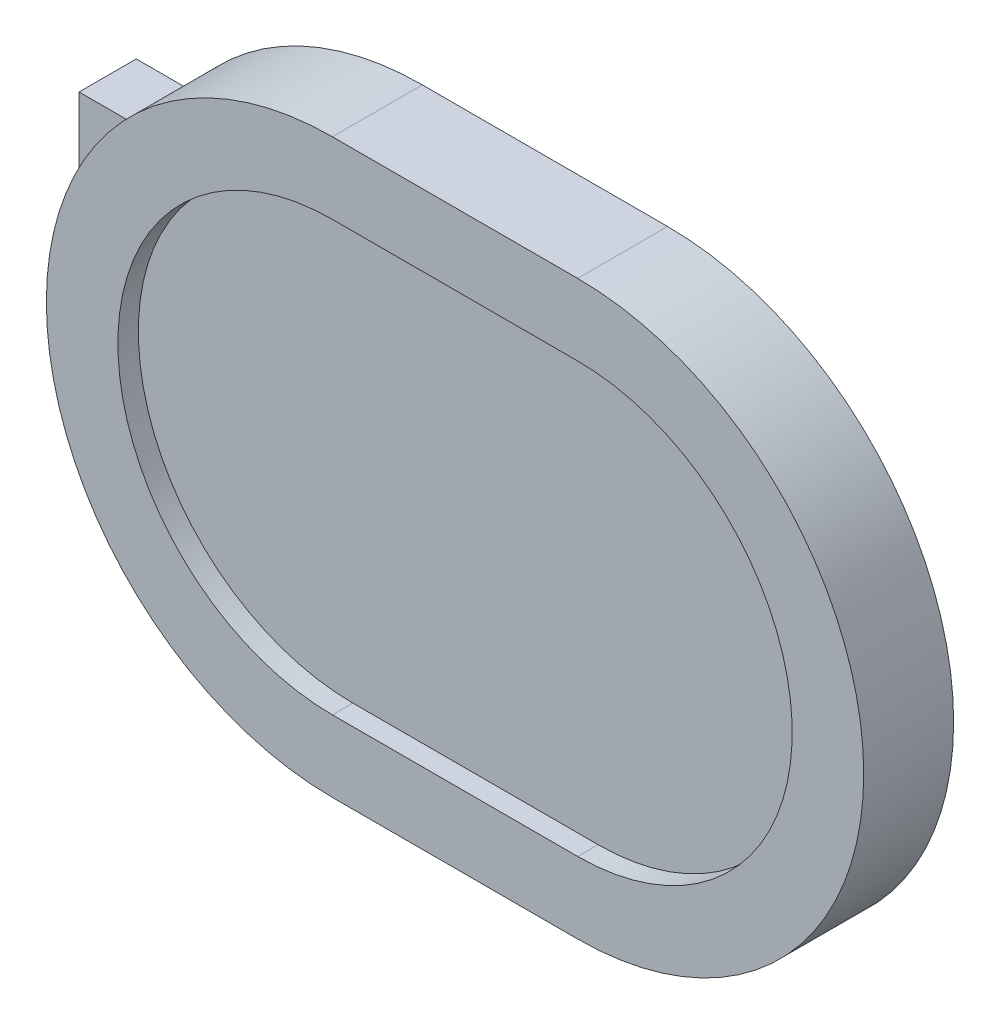
SolidWorks part; units mm, degrees
material "ABS"
ref_plane "Спереди" through (0, 0, 0) normal (0, 0, 1) x (1, 0, 0)
ref_plane "Сверху" through (0, 0, 0) normal (0, 1, 0) x (1, 0, 0)
ref_plane "Справа" through (0, 0, 0) normal (1, 0, 0) x (0, 0, -1)
ref_axis "Ось1" through (0, 0, 50) along (0, 0, -1)
sketch "Эскиз1" plane through (0, 0, 0) normal (0, 0, 1) x (1, 0, 0)
  circle A0 centre (0, 0) radius 5.3
  dimension "D1" = 10.6
extrude "Бобышка-Вытянуть1" add sketch "Эскиз1" along normal blind 0.8
sketch "Эскиз2" plane through (0, 0, 0.8) normal (0, 0, 1) x (1, 0, 0)
  line L0 (3, 0) -> (-3, 0) construction
  line L1 (3, -7) -> (-3, -7)
  line L2 (3, 7) -> (-3, 7)
  arc A0 (3, -7) -> (3, 7) centre (3, 0) ccw
  arc A1 (-3, 7) -> (-3, -7) centre (-3, 0) ccw
  point P2 (0, 0)
  point P7 (-10, 0)
  point P8 (10, 0)
  dimension "D1" = 14
  dimension "D2" = 20
extrude "Бобышка-Вытянуть2" add sketch "Эскиз2" along normal offset from surface (2.2 mm away) 3 up to face at (5.3, 0, 0)
sketch "Эскиз3" plane through (0, 0, 3) normal (0, 0, 1) x (1, 0, 0)
  line L0 (-3, 0) -> (3, 0) construction
  line L1 (-3, 5.25) -> (3, 5.25)
  line L2 (-3, -5.25) -> (3, -5.25)
  arc A0 (-3, 5.25) -> (-3, -5.25) centre (-3, 0) ccw
  arc A1 (3, -5.25) -> (3, 5.25) centre (3, 0) ccw
  point P2 (0, 0)
  point P8 (8.25, 0)
  point P9 (-8.25, 0)
  dimension "D1" = 10.5
  dimension "D2" = 16.5
extrude "Вырез-Вытянуть1" cut sketch "Эскиз3" against normal blind 0.5
sketch "Эскиз5" plane through (0, 0, 0.8) normal (0, 0, -1) x (-1, 0, 0)
  line L0 (8.7094, -4.05) -> (8.7094, 4.05)
  line L1 (8.7094, 4.05) -> (10, 4.05)
  line L2 (10, 4.05) -> (10, -4.05)
  line L3 (10, -4.05) -> (8.7094, -4.05)
  arc A0 (3, -7) -> (3, 7) centre (3, 0) ccw construction
  dimension "D1" = 8.1
extrude "Бобышка-Вытянуть5" add sketch "Эскиз5" against normal offset from surface (1.4 mm away) 0.8 up to face at (0, 0, 3)
sketch "Эскиз4" plane through (0, 0, 0.8) normal (0, 0, -1) x (-1, 0, 0)
  line L4 (9.0646, 0) -> (0, 0) construction
  line L5 (7.2, 1.25) -> (9.7, 1.25)
  line L6 (9.7, 3.75) -> (10, 3.75) construction
  line L7 (7.2, 1.25) -> (7.2, 3.75)
  line L8 (7.2, 3.75) -> (9.7, 3.75)
  line L9 (9.7, 1.25) -> (9.7, 3.75)
  line L10 (7.2, 1.25) -> (9.7, 3.75) construction
  line L11 (7.2, 3.75) -> (9.7, 1.25) construction
  line L12 (10, -4.05) -> (10, 4.05) construction
  line L13 (9.7, 3.75) -> (9.7, 4.05) construction
  line L15 (10, 4.05) -> (8.7094, 4.05) construction
  line L16 (7.2, -1.25) -> (7.2, -3.75)
  line L17 (7.2, -3.75) -> (9.7, -3.75)
  line L18 (9.7, -1.25) -> (9.7, -3.75)
  line L19 (7.2, -1.25) -> (9.7, -1.25)
  point P0 (8.45, 2.5)
  dimension "D1" = 2.5
  dimension "D2" = 0.3
extrude "Бобышка-Вытянуть4" add sketch "Эскиз4" along normal blind 0.2
